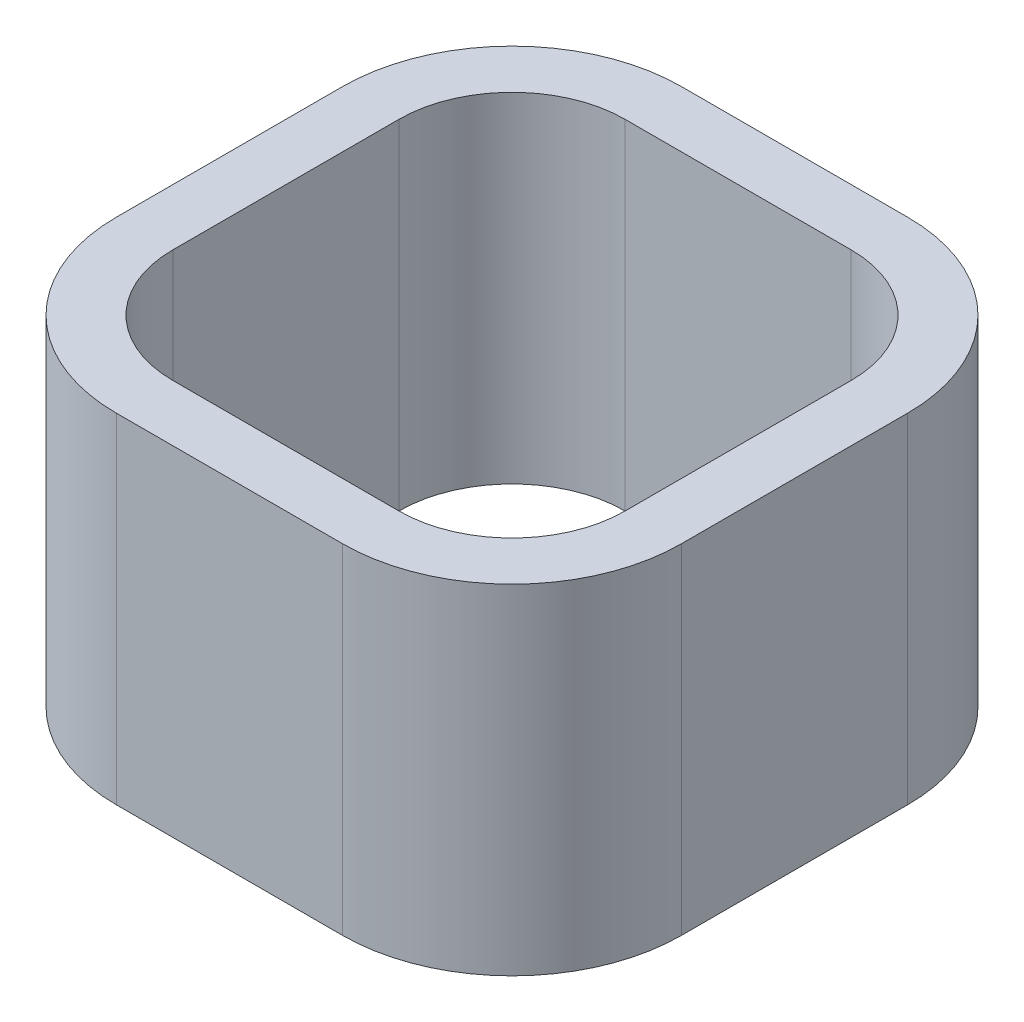
SolidWorks part; units mm, degrees
ref_plane "Ebene vorne" through (0, 0, 0) normal (0, 0, 1) x (1, 0, 0)
ref_plane "Ebene oben" through (0, 0, 0) normal (0, 1, 0) x (1, 0, 0)
ref_plane "Ebene rechts" through (0, 0, 0) normal (1, 0, 0) x (0, 0, -1)
sketch "Skizze1" plane through (0, 0, 0) normal (0, 1, 0) x (1, 0, 0)
  line L0 (-2, 2) -> (2, 2)
  line L1 (-2, 2) -> (-2, -2)
  line L2 (-2, -2) -> (2, -2)
  line L3 (2, 2) -> (2, -2)
  line L4 (-2, 2) -> (2, -2) construction
  line L5 (-2, -2) -> (2, 2) construction
  line L6 (-2.5, 2.5) -> (2.5, 2.5)
  line L7 (-2.5, 2.5) -> (-2.5, -2.5)
  line L8 (-2.5, -2.5) -> (2.5, -2.5)
  line L9 (2.5, 2.5) -> (2.5, -2.5)
  line L10 (-2.5, 2.5) -> (2.5, -2.5) construction
  line L11 (-2.5, -2.5) -> (2.5, 2.5) construction
  point P0 (0, 0)
  point P5 (0, 0)
  dimension "D1" = 4
  dimension "D2" = 4
  dimension "D3" = 5
  dimension "D4" = 5
extrude "Aufsatz-Linear austragen1" add sketch "Skizze1" along normal blind 3
fillet "Verrundung1" radius 1 4 edges at (-2, 1.5, 2) (2, 1.5, 2) (2, 1.5, -2) (-2, 1.5, -2)
fillet "Verrundung2" radius 1.5 4 edges at (2.5, 1.5, 2.5) (-2.5, 1.5, 2.5) (-2.5, 1.5, -2.5) (2.5, 1.5, -2.5)
sketch "Skizze2" plane through (0, 0, 0) normal (0, 1, 0) x (1, 0, 0)
  line L0 (0, 0) -> (0, 4.1213) construction
  line L1 (0, 4.1213) -> (-3.0576, 1.0638) construction
  arc A0 (-1, 2.5) -> (-2.5, 1) centre (-1, 1) ccw construction
  point P3 (0, 0)
  point P5 (0, 4.3338)
  point P9 (0, 0)
  point P10 (-3.0576, 1.0638)
  dimension "D1" = 45
ref_plane "Ebene1" through (-2.0607, 0, -2.0607) normal (-0.7071, 0, -0.7071) x (-0.7071, 0, 0.7071)
sketch "Skizze3" plane through (-2.0607, 0, -2.0607) normal (-0.7071, 0, -0.7071) x (-0.7071, 0, 0.7071)
  line L1 (-1.0607, 0) -> (1.0607, 0) construction
  line L2 (-2.9142, 0) -> (1.4098, 0) construction
  line L3 (1.0607, 3) -> (-1.0607, 3) construction
  point P0 (0, 1.5)
  point P7 (0, 3)
  point P8 (0, 0)
  point P9 (0, 0)
  point P10 (0, 0)
  point P11 (0, 0)
  dimension "D1" = 1.5
  dimension "D2" = 1.5
  dimension "D3" = 1.5
hole_wizard "Ø0.3 (0.3) Durchmesser Bohrung3" positions "Skizze9" profile "Skizze10" hole size "Ø0.3" standard "DIN"
sketch "Skizze9" plane through (-2.0607, 0, -2.0607) normal (-0.7071, 0, -0.7071) x (-0.7071, 0, 0.7071)
  point P0 (0, 1.5)
sketch "Skizze10" plane through (-2.0607, 1.5, -2.0607) normal (0, 1, 0) x (-0.7071, 0, 0.7071)
  line L0 (0, 0) -> (0, 0.16)
  line L1 (0, 0.16) -> (0.15, 0.01)
  line L2 (0.15, 0.01) -> (0.15, 0)
  line L5 (0.15, 0) -> (0, 0)
  line L10 (0, 0.16) -> (-0.15, 0.01) construction
  line L11 (0, -6.35) -> (0, 107.95) construction
  dimension "Bohrerdurchmesser" = 0.3
  dimension "Bohrungstiefe" = 0.01
  dimension "Spitzenwinkel" = 90
